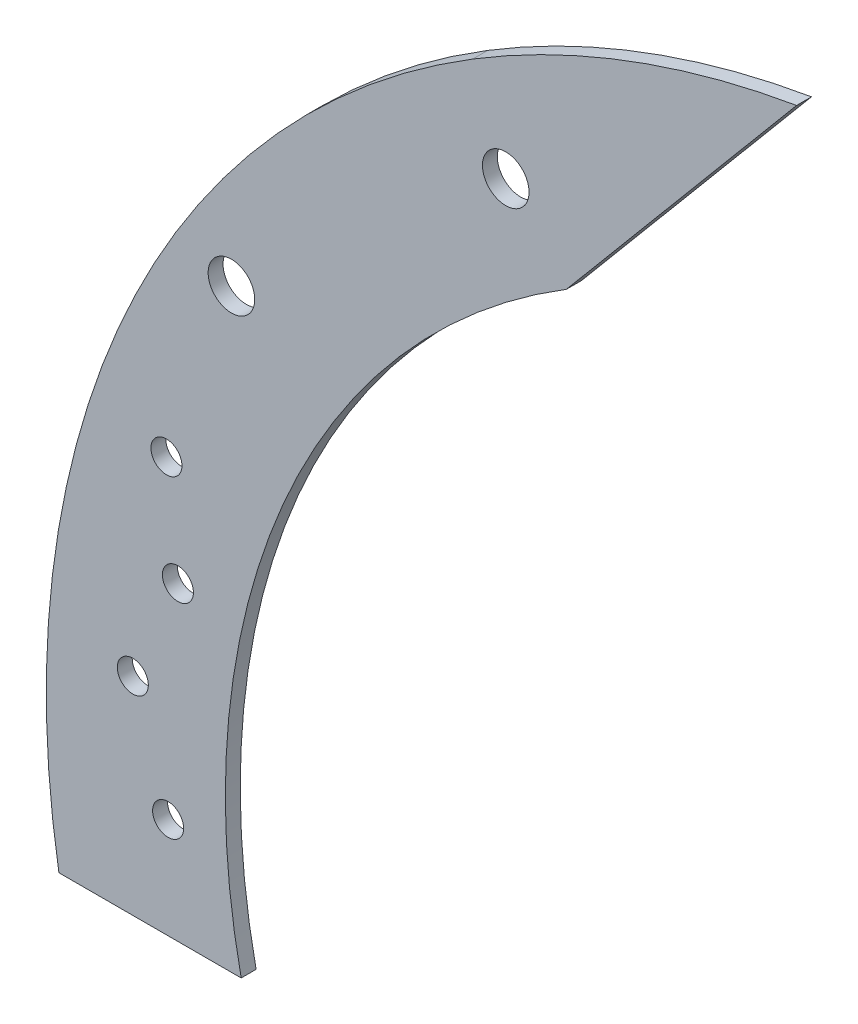
SolidWorks part; units mm, degrees
ref_plane "Front Plane" through (0, 0, 0) normal (0, 0, 1) x (1, 0, 0)
ref_plane "Top Plane" through (0, 0, 0) normal (0, 1, 0) x (1, 0, 0)
ref_plane "Right Plane" through (0, 0, 0) normal (1, 0, 0) x (0, 0, -1)
sketch "Sketch1" plane through (0, 0, 0) normal (0, 0, 1) x (1, 0, 0)
  line L0 (0, -36.5125) -> (-231.5278, -36.5125) construction
  line L1 (-150.6574, -36.5125) -> (-189.4452, -36.5125)
  line L2 (-81.4492, 125.0117) -> (-32.4688, 183.3843)
  circle A0 centre (0, 0) radius 36.5125 construction
  arc A5 (-150.6574, -36.5125) -> (-81.4492, 125.0117) centre (-1.9604, -4.6358) cw
  arc A6 (-189.4452, -36.5125) -> (-101.3638, 157.4927) centre (-1.9604, -4.6358) cw
  arc A7 (-101.3638, 157.4927) -> (-32.4688, 183.3843) centre (0.2073, -8.1713) cw
  dimension "D1" = 73.025
  dimension "D3" = 4.6358
  dimension "D4" = 152.0754
  dimension "D5" = 38.1
  dimension "D6" = 194.3225
  dimension "D2" = 1.9604
  dimension "D7" = 2.1677
  dimension "D8" = 30.5084
  dimension "D9" = 76.2
extrude "Boss-Extrude1" add sketch "Sketch1" along normal blind 3.175
ref_axis "Axis1" through (0, 0, 0) along (0, 0, 1)
sketch "Sketch2" plane through (0, 0, 3.175) normal (0, 0, 1) x (1, 0, 0)
  circle A0 centre (-166.2054, -15.0736) radius 3.302 construction
  circle A1 centre (-164.1258, 29.4335) radius 3.302 construction
  circle A2 centre (-166.2054, -15.0736) radius 3.302
  circle A3 centre (-164.1258, 29.4335) radius 3.302
extrude "Cut-Extrude1" cut sketch "Sketch2" against normal up to surface (3.175 mm away) up to face at (-122.4065, 84.1313, 0)
sketch "Sketch3" plane through (0, 0, 3.175) normal (0, 0, 1) x (1, 0, 0)
  line L0 (-1.9604, -4.6358) -> (1.3579, 3.5895) construction
  line L1 (-189.4452, -36.5125) -> (-149.6704, -36.5125) construction
  line L2 (0, 0) -> (1.3579, 3.5895) construction
  line L3 (-167.8462, -18.1225) -> (-165.4752, 32.6221) construction
  line L4 (-166.6607, 7.2498) -> (-173.7187, 7.5796) construction
  circle A0 centre (-173.7187, 7.5796) radius 3.302
  circle A1 centre (-166.5648, 51.5693) radius 3.302
  arc A2 (-173.7187, 7.5796) -> (-166.5648, 51.5693) centre (0.6789, 1.7948) cw construction
  arc A3 (-81.4492, 125.0117) -> (-150.6574, -36.5125) centre (-1.9604, -4.6358) ccw construction
  arc A4 (-92.3875, 158.4359) -> (-175.1568, -36.5125) centre (1.3579, 3.5895) ccw construction
  arc A5 (-81.4492, 125.0117) -> (-150.6574, -36.5125) centre (-1.9604, -4.6358) ccw construction
  arc A6 (-92.3875, 158.4359) -> (-175.1568, -36.5125) centre (1.3579, 3.5895) ccw construction
  arc A7 (-164.1258, 29.4335) -> (-166.2054, -15.0736) centre (-0.3012, -0.5231) ccw construction
  arc A8 (-80.6589, 131.2575) -> (-149.6704, -36.5125) centre (0, 0) ccw construction
  arc A9 (-80.6589, 131.2575) -> (-149.6704, -36.5125) centre (0, 0) ccw construction
  arc A10 (-101.3638, 157.4927) -> (-189.4452, -36.5125) centre (-1.9604, -4.6358) ccw construction
  arc A11 (-101.3638, 157.4927) -> (-189.4452, -36.5125) centre (-1.9604, -4.6358) ccw construction
  arc A12 (-169.5578, -36.5125) -> (-173.7187, 7.5796) centre (0.6789, 1.7948) cw construction
  point P26 (-166.6607, 7.2498)
  dimension "D1" = 6.604
  dimension "D2" = 50.8
extrude "Cut-Extrude2" cut sketch "Sketch3" against normal up to surface (3.175 mm away) contours A1 | A0 up to face at (-167.4278, 29.4335, 0)
hole_wizard "25/64 (0.39063) Diameter Hole1" positions "Sketch4" profile "Sketch5" hole size "25/64" standard "ANSI Inch" end condition through all
sketch "Sketch4" plane through (0, 0, 3.175) normal (0, 0, 1) x (1, 0, 0)
  line L0 (-94.3609, 138.9343) -> (-152.7335, 89.9538) construction
  line L3 (-81.4492, 125.0117) -> (-32.4688, 183.3843) construction
  point P0 (-94.3609, 138.9343)
  point P2 (-152.7335, 89.9538)
  point P16 (-108.157, 116.4028)
  point P19 (-152.6847, 89.8859)
  dimension "D1" = 76.2
  dimension "D2" = 76.2
  dimension "D3" = 10
  dimension "D4" = 44.45
sketch "Sketch5" plane through (-94.3609, 138.9343, 3.175) normal (1, 0, 0) x (0, -1, 0)
  line L0 (0, 0) -> (0, 3.175)
  line L1 (0, 3.175) -> (4.961, 3.175)
  line L2 (4.961, 3.175) -> (4.961, 0)
  line L5 (4.961, 0) -> (0, 0)
  line L11 (0, -6.35) -> (0, 107.95) construction
  dimension "Thru Hole Dia." = 9.922
  dimension "Thru Hole Depth" = 3.175
